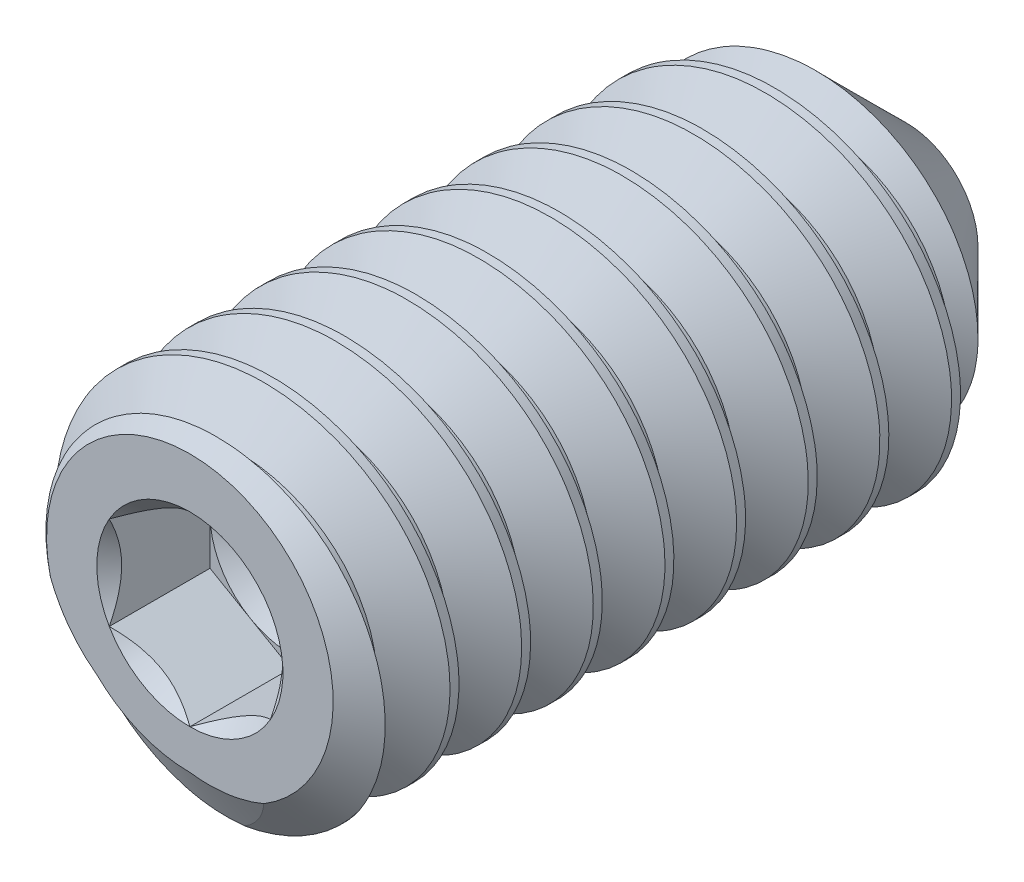
SolidWorks part; units mm, degrees
other "Imported1" parameters "D3"=4.4, "D1"=46.842, "Length"=4, "Drive Size"=0.9, "Thread Size"=2, "Thread Pitch"=0.4, "D2"=0.0866, "hex Depth"=0.5625, "Dia"=12, "D4"=2.3829, "Cup Point Dia"=3.3528, "D5"=1.436, "D6"=1.4986, "D7"=5.0014, "Pitch"=1.75
ref_plane "Front" through (0, 0, 0) normal (0, 0, 1) x (1, 0, 0)
ref_plane "Top" through (0, 0, 0) normal (0, 1, 0) x (1, 0, 0)
ref_plane "Right" through (0, 0, 0) normal (1, 0, 0) x (0, 0, -1)
sketch "Sketch1" plane through (0, 0, 0) normal (1, 0, 0) x (0, 0, -1)
  line L0 (2, 1) -> (-2, 1) construction
  line L1 (-2, 1) -> (-2, -1) construction
  line L2 (-2, -1) -> (2, -1) construction
  line L3 (2, -1) -> (2, 1) construction
  line L4 (-2, 0.45) -> (-2, -0.45) construction
  line L5 (1.975, 1.0433) -> (2.375, 1.0433) construction
  line L6 (1.975, 1.0433) -> (2, 1) construction
  line L7 (2, 1) -> (2.35, 1) construction
  line L8 (2.35, 1) -> (2.375, 1.0433) construction
  line L9 (2, 1) -> (2.175, 0.6969) construction
  line L10 (2.175, 0.6969) -> (2.35, 1) construction
  line L11 (2.15, 0.7402) -> (2.2, 0.7402) construction
  line L12 (2.175, 1.0433) -> (2.175, 1) construction
  line L13 (2.175, 0.7402) -> (2.175, 0.6969) construction
  point P3 (0, 1)
  point P24 (-2, 0)
  point P25 (-2, 0)
  dimension "D1" = 0.05
sketch "Sketch11" plane through (0, 0, 0) normal (1, 0, 0) x (0, 0, -1)
  line L0 (-2, 0) -> (-2, 0.8)
  line L1 (-2, 0.8) -> (-1.86, 1)
  line L2 (-1.86, 1) -> (1.4, 1)
  line L3 (1.4, 1) -> (2, 0.4)
  line L4 (2, 0.4) -> (1.7597, 0)
  line L5 (1.7597, 0) -> (-2, 0)
  line L6 (1.7597, 0) -> (2, 0) construction
  line L7 (2, 0) -> (2, 0.4) construction
  line L8 (2, -0.4) -> (1.7597, 0) construction
  line L9 (-1.86, -1) -> (1.4, -1) construction
  line L10 (-2, -1) -> (2, -1) construction
  line L11 (-2, 1) -> (-2, -1) construction
  line L12 (2, -1) -> (2, 1) construction
  point P11 (0.6, -1)
  point P12 (-2, 1)
  dimension "D3" = 35
  dimension "D5" = 118
  dimension "D6" = 45
  dimension "D1" = 0.2
  dimension "D2" = 1.4
  dimension "D4" = 0.6
revolve "Revolve1" add sketch "Sketch11" angle 360 about L6
sketch "Sketch2" plane through (0, 0, 2) normal (0, 0, 1) x (1, 0, 0)
  line L1 (0, 0.5196) -> (-0.45, 0.2598)
  line L2 (-0.45, 0.2598) -> (-0.45, -0.2598)
  line L3 (-0.45, -0.2598) -> (0, -0.5196)
  line L4 (0, -0.5196) -> (0.45, -0.2598)
  line L5 (0.45, -0.2598) -> (0.45, 0.2598)
  line L6 (0.45, 0.2598) -> (0, 0.5196)
  circle A0 centre (0, 0) radius 0.45 construction
  circle A1 centre (0, 0) radius 1 construction
extrude "Cut-Extrude1" cut sketch "Sketch2" against normal blind 0.5625
sketch "Sketch3" plane through (0, 0, 2) normal (0, 0, 1) x (1, 0, 0)
  circle A0 centre (0, 0) radius 0.5196
extrude "Cut-Extrude2" cut sketch "Sketch3" against normal through all draft 45
sketch "Sketch4" plane through (0, 0, 1.4375) normal (0, 0, 1) x (1, 0, 0)
  circle A0 centre (0, 0) radius 0.45 construction
  circle A1 centre (0, 0) radius 0.45
extrude "Cut-Extrude3" cut sketch "Sketch4" against normal through all draft 60
sketch "Sketch13" plane through (0, 0, 0) normal (1, 0, 0) x (0, 0, -1)
  line L0 (0, -1) -> (0, 1) construction
  line L2 (-1.86, 1) -> (1.4, 1) construction
  line L4 (1.7597, 0) -> (-2, 0) construction
  point P0 (-0.2403, 0)
  point P4 (0, 0)
  point P9 (0.2403, 0)
  dimension "D1" = 2
ref_plane "Plane1" through (0, 0, -2) normal (0, 0, 1) x (1, 0, 0)
sketch "Sketch5" plane through (0, 0, -2) normal (0, 0, 1) x (1, 0, 0)
  circle A0 centre (0, 0) radius 1 construction
  circle A1 centre (0, 0) radius 1
curve "Helix/Spiral1" pitch 0.4 height 4.4 radius 1 centre (0, 0, -2) axis (0, 0, 1) start towards (0, 1, 0)
sketch "Sketch6" plane through (0, 0, 0) normal (1, 0, 0) x (0, 0, -1)
  line L0 (1.9875, 1.0217) -> (2.3625, 1.0217)
  line L1 (1.975, 1.0433) -> (2, 1) construction
  line L2 (2.35, 1) -> (2.375, 1.0433) construction
  line L3 (2.3625, 1.0217) -> (2.2, 0.7402)
  line L4 (2.2, 0.7402) -> (2.15, 0.7402)
  line L5 (2.15, 0.7402) -> (1.9875, 1.0217)
sweep "Cut-Sweep1" cut profiles "Sketch6" path "Helix/Spiral1"
equation "\"D3@Helix/Spiral1\" = \"Length@Sketch1\" * 1.1"
equation "\"hex Depth@Cut-Extrude1\"=\"Drive Size@Sketch1\" * .625"
equation "\"D1@Sketch11\" = \"Thread Pitch@Sketch1\" * .5"
equation "\"D2@Sketch11\" = \"Thread Pitch@Sketch1\" * 3.5"
equation "\"D1@Helix/Spiral1\" = \"Thread Pitch@Sketch1\""
equation "\"D4@Sketch11\" = \"Thread Pitch@Sketch1\" * 1.5"
equation "\"D1@Sketch1\" = \"Thread Pitch@Sketch1\" / 8"
equation "\"D1@Sketch13\"=\"Thread Size@Sketch1\""
